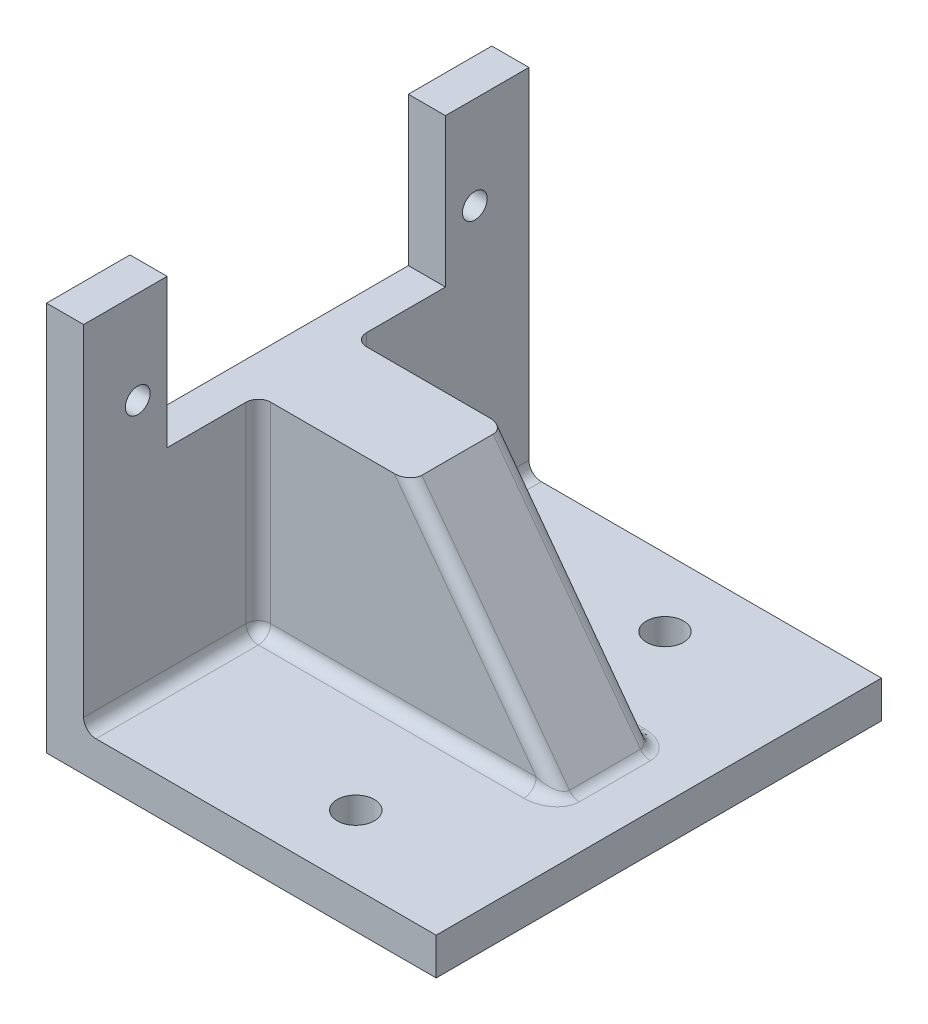
SolidWorks part; units mm, degrees
ref_plane "Front Plane" through (0, 0, 0) normal (0, 0, 1) x (1, 0, 0)
ref_plane "Top Plane" through (0, 0, 0) normal (0, 1, 0) x (1, 0, 0)
ref_plane "Right Plane" through (0, 0, 0) normal (1, 0, 0) x (0, 0, -1)
sketch "Sketch1" plane through (0, 0, 0) normal (0, 0, 1) x (1, 0, 0)
  line L0 (0, 30) -> (0, 0)
  line L1 (0, 0) -> (30, 0)
  dimension "D1" = 30
  dimension "D2" = 30
extrude "Extrude-Thin1" add sketch "Sketch1" along normal blind 36 thin thin type mid plane wall 3
sketch "Sketch2" plane through (-1.5, 0, 0) normal (-1, 0, 0) x (0, 0, 1)
  line L0 (18, -1.5) -> (18, 30) construction
  line L1 (6.75, 30) -> (29.25, 30)
  line L2 (6.75, 30) -> (6.75, 18)
  line L3 (6.75, 18) -> (29.25, 18)
  line L4 (29.25, 30) -> (29.25, 18)
  line L5 (36, -1.5) -> (0, -1.5) construction
  line L6 (36, 30) -> (0, 30) construction
  dimension "D1" = 22.5
  dimension "D2" = 12
extrude "Cut-Extrude1" cut sketch "Sketch2" against normal blind 10
sketch "Sketch3" plane through (-1.5, 0, 0) normal (-1, 0, 0) x (0, 0, 1)
  line L0 (18, -1.5) -> (18, 30.1378) construction
  line L1 (36, -1.5) -> (0, -1.5) construction
  circle A0 centre (31.625, 22.5077) radius 1
  circle A1 centre (4.375, 22.5077) radius 1
  dimension "D1" = 2
  dimension "D3" = 27.25
extrude "Cut-Extrude2" cut sketch "Sketch3" against normal blind 10
sketch "Sketch4" plane through (0, 1.5, 0) normal (0, 1, 0) x (1, 0, 0)
  line L0 (1.5, -18) -> (30, -18) construction
  line L1 (1.5, -36) -> (1.5, 0) construction
  line L2 (30, -36) -> (30, 0) construction
  line L3 (1.5, -21.8751) -> (25.948, -21.8751)
  line L5 (25.948, -14.1249) -> (1.5, -14.1249)
  line L7 (25.948, -21.8751) -> (25.948, -14.1249)
  line L8 (1.5, -21.8751) -> (1.5, -14.1249)
extrude "Boss-Extrude1" add sketch "Sketch4" along normal up to vertex (16.5 mm away) up to point (1.5, 18, 6.75)
sketch "Sketch5" plane through (0, 0, 21.8751) normal (0, 0, 1) x (1, 0, 0)
  line L0 (25.948, 1.5) -> (13.724, 18)
  line L1 (1.5, 18) -> (25.948, 18) construction
  line L2 (13.724, 18) -> (25.948, 18)
  line L3 (25.948, 18) -> (25.948, 1.5) construction
  line L4 (25.948, 18) -> (25.948, 1.5)
extrude "Cut-Extrude3" cut sketch "Sketch5" against normal blind 16
sketch "Sketch6" plane through (0, 1.5, 0) normal (0, 1, 0) x (1, 0, 0)
  line L1 (30, -18) -> (25.948, -18) construction
  line L2 (30, -36) -> (30, 0) construction
  line L3 (25.948, -21.8751) -> (25.948, -14.1249) construction
  circle A0 centre (18, -30.5) radius 1.5
  circle A1 centre (18, -5.5) radius 1.5
  dimension "D1" = 3
  dimension "D2" = 12
  dimension "D3" = 25
extrude "Cut-Extrude4" cut sketch "Sketch6" against normal through all
fillet "Fillet1" radius 1 9 edges at (1.5, 9.75, 21.8751) (1.5, 9.75, 14.1249) (1.5, 1.5, 7.0624) (1.5, 1.5, 28.9376) (13.724, 1.5, 14.1249) (19.836, 9.75, 14.1249) (19.836, 9.75, 21.8751) (25.948, 1.5, 18) (13.724, 1.5, 21.8751)
